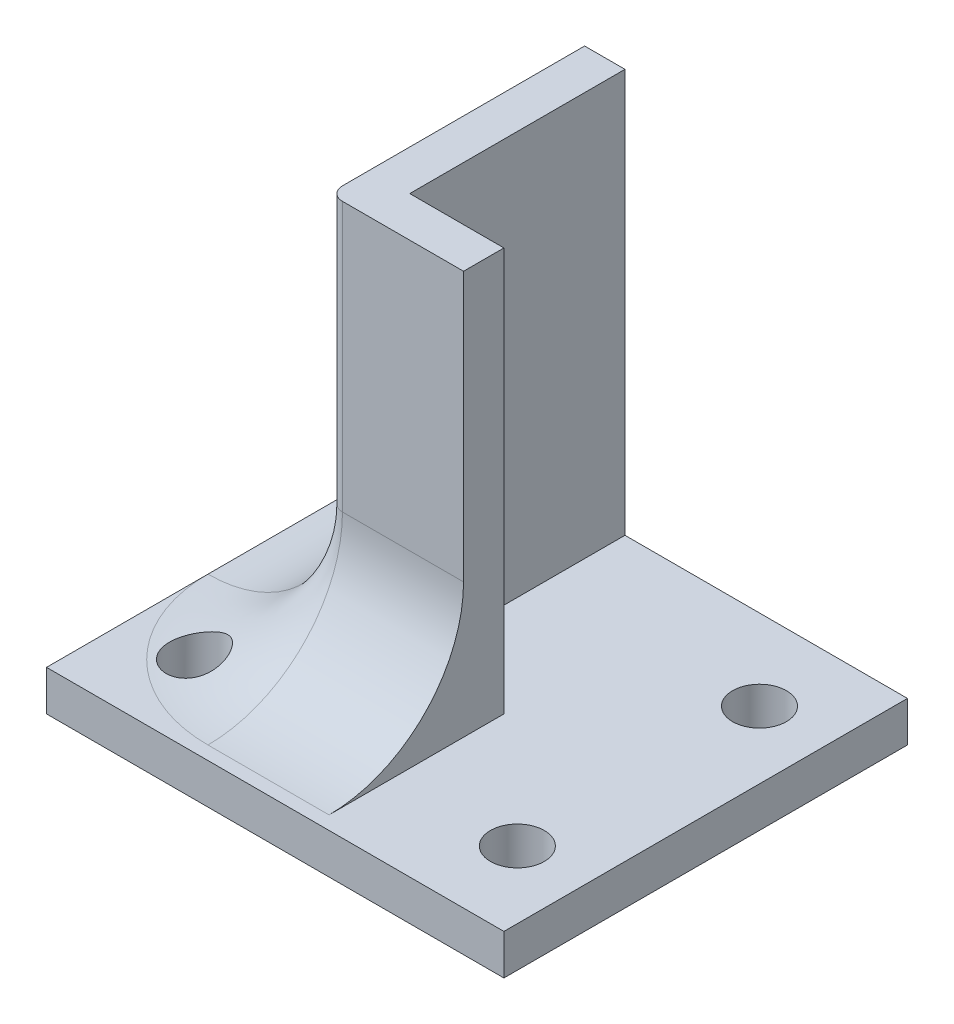
SolidWorks part; units mm, degrees
ref_plane "Front Plane" through (0, 0, 0) normal (0, 0, 1) x (1, 0, 0)
ref_plane "Top Plane" through (0, 0, 0) normal (0, 1, 0) x (1, 0, 0)
ref_plane "Right Plane" through (0, 0, 0) normal (1, 0, 0) x (0, 0, -1)
sketch "Sketch1" plane through (-298.9537, 67.3536, 0) normal (0, 0, 1) x (1, 0, 0)
  line L10 (298.9537, -64.3536) -> (298.9537, -67.3536)
  line L11 (298.9537, -67.3536) -> (332.9537, -67.3536)
  line L12 (332.9537, -67.3536) -> (332.9537, -64.3536)
  line L13 (332.9537, -64.3536) -> (298.9537, -64.3536)
  dimension "D1" = 34
  dimension "D4" = 3
extrude "Boss-Extrude1" add sketch "Sketch1" along normal blind 30
sketch "Sketch2" plane through (0, 3, 0) normal (0, 1, 0) x (1, 0, 0)
  line L0 (29, -6) -> (29, 0) construction
  line L1 (0, -30) -> (0, 0) construction
  line L2 (29, -24) -> (29, -30) construction
  line L3 (34, -30) -> (0, -30) construction
  line L4 (34, 0) -> (0, 0) construction
  line L5 (34, -6) -> (29, -6) construction
  line L6 (34, -30) -> (34, 0) construction
  line L7 (29, -6) -> (5, -6) construction
  line L8 (5, -6) -> (0, -6) construction
  circle A0 centre (29, -6) radius 2
  circle A1 centre (29, -24) radius 2
  dimension "D1" = 4
  dimension "D2" = 24
  dimension "D3" = 18
extrude "Cut-Extrude1" cut sketch "Sketch2" against normal up to surface (3 mm away) up to face at (17, 0, 15)
ref_plane "Plane1" through (17, 0, 0) normal (1, 0, 0) x (0, 0, -1)
mirror "Mirror1" about plane through (17, 0, 0) normal (1, 0, 0) of "Cut-Extrude1"
sketch "Sketch3" plane through (0, 3, 0) normal (0, 1, 0) x (1, 0, 0)
  line L0 (10, 0) -> (10, -19)
  line L1 (34, 0) -> (0, 0) construction
  line L2 (10, -19) -> (20, -19)
  line L3 (20, -19) -> (20, -16)
  line L4 (20, -16) -> (13, -16)
  line L5 (13, -16) -> (13, 0)
  line L6 (17, -1.65) -> (17, 1.65) construction
  line L7 (10, 0) -> (13, 0)
  dimension "D1" = 3
  dimension "D2" = 4
  dimension "D3" = 3
  dimension "D4" = 3
  dimension "D5" = 16
extrude "Boss-Extrude2" add sketch "Sketch3" along normal blind 30
fillet "Fillet1" radius 1 1 edges at (10, 18, 19)
fillet "Fillet2" radius 10 3 edges at (10, 3, 9) (10.2929, 3, 18.7071) (15.5, 3, 19)
